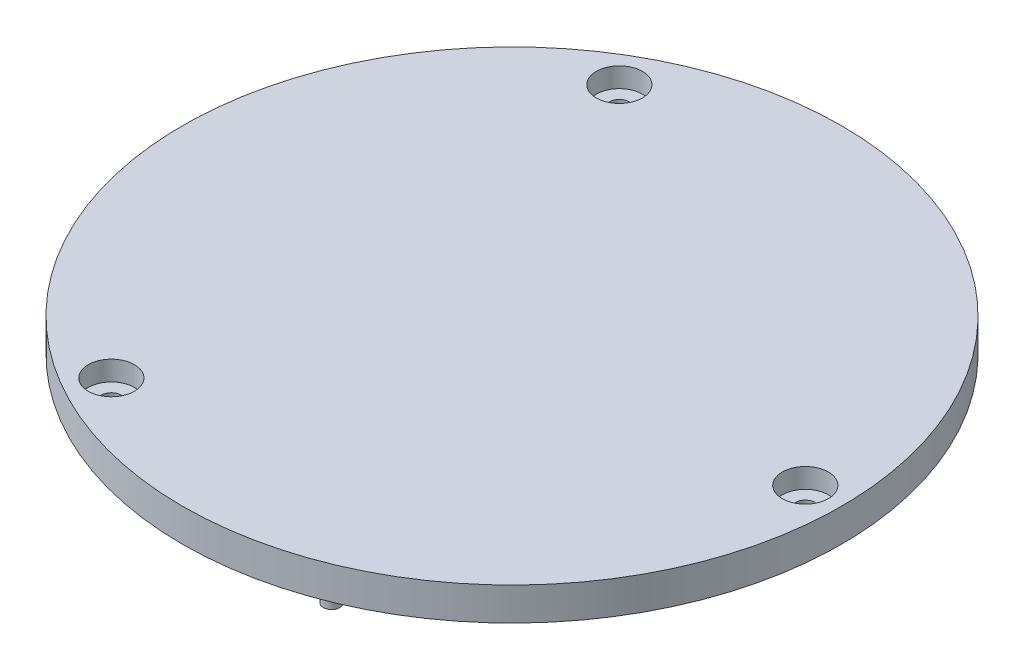
SolidWorks part; units mm, degrees
note: '?' marks a value the reader was unsure of.
ref_plane "Alzado" through (0, 0, 0) normal (0, 0, 1) x (1, 0, 0)
ref_plane "Planta" through (0, 0, 0) normal (0, 1, 0) x (1, 0, 0)
ref_plane "Vista lateral" through (0, 0, 0) normal (1, 0, 0) x (0, 0, -1)
sketch "Croquis1" plane through (0, 0, 0) normal (0, 1, 0) x (1, 0, 0)
  circle A0 centre (0, 0) radius 50
  dimension "D1" = 100
extrude "Saliente-Extruir1" add sketch "Croquis1" along normal blind 5
sketch "Croquis2" plane through (0, 5, 0) normal (0, 1, 0) x (1, 0, 0)
  line L0 (0, 0) -> (50, 0) construction
  circle A0 centre (0, 0) radius 50 construction
  circle A1 centre (44.5, 0) radius 1.5
  dimension "D1" = 3
  dimension "D2" = 44.5
extrude "Cortar-Extruir1" cut sketch "Croquis2" against normal blind 5
ref_axis "Eje1" through (0, -0.25, 0) along (0, 1, 0)?
sketch "Croquis3" plane through (0, 5, 0) normal (0, 1, 0) x (1, 0, 0)
  circle A0 centre (44.5, 0) radius 1.5 construction
  circle A1 centre (44.5, 0) radius 1.5 construction
  circle A2 centre (44.5, 0) radius 3.5
  dimension "D1" = 2
extrude "Cortar-Extruir2" cut sketch "Croquis3" against normal blind 3
pattern_circular "MatrizC2" count 3 over 360 about axis through (0, 0, 0) along (0, 1, 0) of "Cortar-Extruir2", "Cortar-Extruir1"
sketch "Croquis4" plane through (0, 0, 0) normal (0, -1, 0) x (1, 0, 0)
  line L0 (-32, 14.7) -> (-32, -14.7) construction
  line L1 (0, 0) -> (-32, 0) construction
  line L2 (-46, -8.7) -> (-18, -8.7) construction
  line L3 (-46, -8.7) -> (-46, 8.7) construction
  line L4 (-46, 8.7) -> (-18, 8.7) construction
  line L5 (-18, -8.7) -> (-18, 8.7) construction
  line L6 (-46, -8.7) -> (-18, 8.7) construction
  line L7 (-46, 8.7) -> (-18, -8.7) construction
  circle A0 centre (0, 0) radius 48 construction
  circle A1 centre (-32, 14.7) radius 3
  circle A2 centre (-32, -14.7) radius 3
  point P5 (-32, 0)
  dimension "D1" = 96
  dimension "D5" = 6
  dimension "D2" = 17.4
  dimension "D3" = 28
  dimension "D4" = 32
  dimension "D6" = 14.7
extrude "Saliente-Extruir2" add sketch "Croquis4" along normal blind 5
sketch "Croquis6" plane through (0, 0, 0) normal (0, -1, 0) x (1, 0, 0)
  line L0 (0, 0) -> (20.2032, 11.6643) construction
  line L5 (-18, -17.3205) -> (28.1072, 9.2995) construction
  line L6 (-18, -17.3205) -> (-5.3, -39.3176) construction
  line L7 (28.1072, 9.2995) -> (40.8072, -12.6976) construction
  line L8 (-5.3, -39.3176) -> (40.8072, -12.6976) construction
  line L9 (-18, -17.3205) -> (40.8072, -12.6976) construction
  line L10 (28.1072, 9.2995) -> (-5.3, -39.3176) construction
  line L11 (0, 0) -> (0, 21.0188) construction
  circle A0 centre (27.1738, 5.8161) radius 2.55
  circle A1 centre (37.3238, -11.7642) radius 2.55
  circle A2 centre (-14.5166, -18.2539) radius 2.55
  circle A3 centre (-4.3666, -35.8342) radius 2.55
  point P3 (11.4036, -15.009)
  dimension "D6" = 5.1
  dimension "D1" = 25.4
  dimension "D2" = 53.24
  dimension "D3" = 60
  dimension "D4" = 6
  dimension "D5" = 18
extrude "Saliente-Extruir4" add sketch "Croquis6" along normal blind 2
sketch "Croquis7" plane through (0, 0, 0) normal (0, -1, 0) x (1, 0, 0)
  line L0 (27.1738, 5.8161) -> (-14.5166, -18.2539) construction
  line L1 (34.0811, 25.9698) -> (-13.5503, -1.5302) construction
  line L2 (-16.3003, 3.233) -> (-10.8003, -6.2933) construction
  line L3 (2.1901, 1.2067) -> (23.8407, 13.7067)
  line L4 (2.1901, 1.2067) -> (-3.3099, 10.733)
  line L5 (23.8407, 13.7067) -> (18.3407, 23.233)
  line L6 (-3.3099, 10.733) -> (18.3407, 23.233)
  point P8 (-13.5503, -1.5302)
  point P9 (-0.5599, 5.9698)
  dimension "D1" = 55
  dimension "D2" = 11
  dimension "D3" = 14
  dimension "D4" = 2.5
  dimension "D5" = 15
  dimension "D6" = 25
extrude "Saliente-Extruir5" add sketch "Croquis7" along normal blind 12
sketch "Croquis8" plane through (23.8157, 0, 13.75) normal (0.866, 0, 0.5) x (0.5, 0, -0.866)
  line L0 (0.05, -12) -> (-10.95, -12) construction
  line L1 (-1.45, -12) -> (-9.45, -12)
  line L3 (-1.45, -12) -> (-1.45, -7)
  line L4 (-1.45, -7) -> (-9.45, -7)
  line L5 (-9.45, -7) -> (-9.45, -12)
  line L7 (-10.95, -12) -> (-10.95, 0) construction
  line L8 (-9.45, -12) -> (-1.45, -12)
  dimension "D1" = 8
  dimension "D2" = 1.5
  dimension "D3" = 5
extrude "Cortar-Extruir3" cut sketch "Croquis8" against normal blind 25 and the other way through all contours L3 L4 L5
sketch "Croquis9" plane through (-5.475, 0, 9.483) normal (-0.5, 0, 0.866) x (0.866, 0, 0.5)
  line L0 (2.5, -4) -> (27.5, -4) construction
  line L1 (2.5, -12) -> (2.5, 0) construction
  line L2 (27.5, -12) -> (27.5, 0) construction
  line L3 (27.5, -7) -> (2.5, -7) construction
  line L4 (15, -4) -> (15, -6.93) construction
  line L5 (5, -4.75) -> (10, -4.75)
  line L6 (5, -4.75) -> (5, -3.25)
  line L7 (5, -3.25) -> (10, -3.25)
  line L8 (10, -4.75) -> (10, -3.25)
  line L9 (5, -4.75) -> (10, -3.25) construction
  line L10 (5, -3.25) -> (10, -4.75) construction
  line L11 (25, -3.25) -> (20, -3.25)
  line L12 (20, -4.75) -> (20, -3.25)
  line L13 (25, -4.75) -> (20, -4.75)
  line L14 (25, -4.75) -> (25, -3.25)
  point P8 (7.5, -4)
  point P13 (15, -4)
  dimension "D1" = 3
  dimension "D2" = 5
  dimension "D3" = 1.5
  dimension "D4" = 5
extrude "Cortar-Extruir4" cut sketch "Croquis9" against normal blind 11
fillet "Redondeo1" radius 1.5 2 edges at (8.2654, -7, 15.6839) (12.2654, -7, 8.7557)
sketch "Croquis10" plane through (0, 0, 0) normal (0, -1, 0) x (1, 0, 0)
  line L0 (-13.4282, 7.2583) -> (-27.4282, 31.507) construction
  line L1 (-13.4282, 7.2583) -> (10.8205, 21.2583) construction
  line L2 (-27.4282, 31.507) -> (-3.1795, 45.507) construction
  line L3 (10.8205, 21.2583) -> (-3.1795, 45.507) construction
  line L4 (18.3407, 23.233) -> (-3.3099, 10.733) construction
  line L5 (18.3407, 23.233) -> (-3.3099, 10.733) construction
  line L6 (-20.4282, 19.3827) -> (3.8205, 33.3827) construction
  line L7 (3.8205, 33.3827) -> (9.0167, 36.3827) construction
  line L8 (-1.3038, 14.2583) -> (-15.3038, 38.507) construction
  line L9 (0, 0) -> (-20.3848, -11.7691) construction
  line L10 (0, 0) -> (-5.5145, 9.5515) construction
  circle A0 centre (9.0167, 36.3827) radius 3
  circle A1 centre (-25.6244, 16.3827) radius 3
  dimension "D2" = 6
  dimension "D5" = 6
  dimension "D1" = 28
  dimension "D3" = 8
  dimension "D4" = 13
extrude "Saliente-Extruir6" add sketch "Croquis10" along normal blind 5
sketch "Croquis5" plane through (0, -5, 0) normal (0, -1, 0) x (1, 0, 0)
  circle A1 centre (9.0167, 36.3827) radius 3 construction
  circle A6 centre (-25.6244, 16.3827) radius 3 construction
  circle A7 centre (-32, 14.7) radius 3 construction
  circle A18 centre (-32, -14.7) radius 3 construction
  circle A19 centre (9.0167, 36.3827) radius 3 construction
  circle A28 centre (-25.6244, 16.3827) radius 3 construction
  circle A29 centre (-32, 14.7) radius 3 construction
  circle A30 centre (-32, -14.7) radius 3 construction
  circle A31 centre (9.0167, 36.3827) radius 1.25
  circle A32 centre (-25.6244, 16.3827) radius 1.25
  circle A33 centre (-32, 14.7) radius 1.25
  circle A34 centre (-32, -14.7) radius 1.25
  dimension "D2" = 1.75
extrude "Saliente-Extruir7" add sketch "Croquis5" along normal blind 5
sketch "Croquis12" plane through (0, -2, 0) normal (0, -1, 0) x (1, 0, 0)
  circle A0 centre (-14.5166, -18.2539) radius 2.55 construction
  circle A1 centre (-4.3666, -35.8342) radius 2.55 construction
  circle A2 centre (37.3238, -11.7642) radius 2.55 construction
  circle A3 centre (27.1738, 5.8161) radius 2.55 construction
  circle A4 centre (-14.5166, -18.2539) radius 2.55 construction
  circle A5 centre (-4.3666, -35.8342) radius 2.55 construction
  circle A6 centre (37.3238, -11.7642) radius 2.55 construction
  circle A7 centre (27.1738, 5.8161) radius 2.55 construction
  circle A8 centre (27.1738, 5.8161) radius 1.05
  circle A9 centre (37.3238, -11.7642) radius 1.05
  circle A10 centre (-4.3666, -35.8342) radius 1.05
  circle A11 centre (-14.5166, -18.2539) radius 1.05
  dimension "D1" = 1.5
extrude "Saliente-Extruir8" add sketch "Croquis12" along normal blind 5
sketch "Croquis11" plane through (0, 0, 0) normal (0, -1, 0) x (1, 0, 0)
  line L0 (-22.25, 38.5381) -> (0, 0) construction
  line L1 (0, 0) -> (24, -41.5692) construction
  line L2 (29.8452, -37.5934) -> (17.6342, -44.6434) construction
  line L3 (17.6342, -44.6434) -> (10.1342, -31.653) construction
  line L4 (10.1342, -31.653) -> (22.3452, -24.603) construction
  line L5 (22.3452, -24.603) -> (29.8452, -37.5934) construction
  line L6 (12.9842, -36.5894) -> (25.1952, -29.5394) construction
  circle A0 centre (0, 0) radius 48 construction
  circle A1 centre (0, 0) radius 48 construction
  circle A2 centre (15.3225, -35.2394) radius 2.5
  circle A3 centre (22.8569, -30.8894) radius 2.5
  point P8 (23.7397, -41.1184)
  dimension "D4" = 2.7
  dimension "D5" = 5
  dimension "D1" = 14.1
  dimension "D2" = 15
  dimension "D3" = 5.7
extrude "Saliente-Extruir9" add sketch "Croquis11" along normal blind 4
sketch "Croquis13" plane through (0, -4, 0) normal (0, -1, 0) x (1, 0, 0)
  circle A0 centre (22.8569, -30.8894) radius 2.5 construction
  circle A2 centre (15.3225, -35.2394) radius 2.5 construction
  circle A3 centre (22.8569, -30.8894) radius 2.5 construction
  circle A4 centre (15.3225, -35.2394) radius 2.5 construction
  circle A5 centre (22.8569, -30.8894) radius 1
  circle A6 centre (15.3225, -35.2394) radius 1
  dimension "D1" = 1.5
extrude "Saliente-Extruir10" add sketch "Croquis13" along normal blind 5
equation "\"D6@Croquis4\"=\"D2@Croquis4\"/2+\"D5@Croquis4\""
